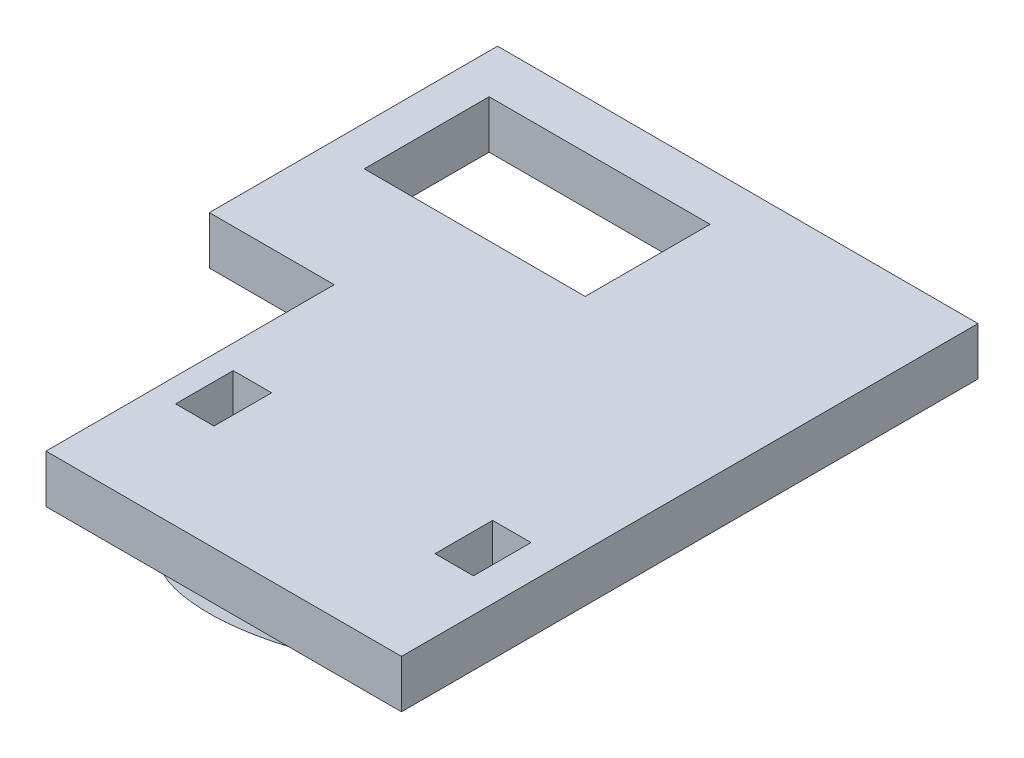
SolidWorks part; units mm, degrees
ref_plane "前视基准面" through (0, 0, 0) normal (0, 0, 1) x (1, 0, 0)
ref_plane "上视基准面" through (0, 0, 0) normal (0, 1, 0) x (1, 0, 0)
ref_plane "右视基准面" through (0, 0, 0) normal (1, 0, 0) x (0, 0, -1)
other "Configuration Table"
sketch "草图1" plane through (0, 0, 0) normal (0, 1, 0) x (1, 0, 0)
  line L0 (-12, 0) -> (-25, 0)
  line L1 (0, -30) -> (25, -30)
  line L2 (-25, 0) -> (-25, 30)
  line L3 (-25, 30) -> (25, 30)
  line L4 (25, -30) -> (25, 30)
  line L5 (-12, 0) -> (-12, -30)
  line L6 (-12, -30) -> (0, -30)
  point P0 (0, 0)
  dimension "D1" = 50
extrude "凸台-拉伸1" add sketch "草图1" along normal blind 5
sketch "草图3" plane through (0, 5, 0) normal (0, 1, 0) x (1, 0, 0)
  line L0 (25, 30) -> (-25, 30) construction
  line L1 (-20.8838, 25) -> (2.1162, 25)
  line L2 (-20.8838, 25) -> (-20.8838, 12)
  line L3 (-20.8838, 12) -> (2.1162, 12)
  line L4 (2.1162, 25) -> (2.1162, 12)
  line L5 (-20.8838, 25) -> (2.1162, 12) construction
  line L6 (-20.8838, 12) -> (2.1162, 25) construction
  point P0 (-9.3838, 18.5)
  dimension "D1" = 13
  dimension "D2" = 23
  dimension "D3" = 5
extrude "切除-拉伸1" cut sketch "草图3" against normal through all
sketch "草图4" plane through (0, 5, 0) normal (0, 1, 0) x (1, 0, 0)
  line L0 (17.4849, -13) -> (21.4849, -13)
  line L1 (-9.5151, -13) -> (-5.5151, -13)
  line L2 (-9.5151, -13) -> (-9.5151, -19)
  line L3 (-9.5151, -19) -> (-5.5151, -19)
  line L4 (-5.5151, -13) -> (-5.5151, -19)
  line L5 (-9.5151, -13) -> (-5.5151, -19) construction
  line L6 (-9.5151, -19) -> (-5.5151, -13) construction
  line L7 (17.4849, -13) -> (17.4849, -19)
  line L8 (17.4849, -19) -> (21.4849, -19)
  line L9 (21.4849, -13) -> (21.4849, -19)
  line L10 (-20.8838, 12) -> (2.1162, 12) construction
  line L11 (-12, -30) -> (25, -30) construction
  point P0 (-7.5151, -16)
  dimension "D1" = 23
  dimension "D2" = 25
  dimension "D3" = 6
  dimension "D4" = 4
  dimension "D5" = 11
extrude "切除-拉伸3" cut sketch "草图4" against normal up to next
ref_plane "基准面2" through (0, -5, 0) normal (0, -1, 0) x (-1, 0, 0)
sketch "草图7" plane through (0, -5, 0) normal (0, -1, 0) x (-1, 0, 0)
  line L0 (12, -13.3987) -> (-12, -13.3987) construction
ref_plane "基准面3" through (0, -8.7214, 3.1743) normal (0, -0.9397, 0.342) x (1, 0, 0)
sketch "草图2" plane through (0, 0, 0) normal (0, -1, 0) x (1, 0, 0)
  line L0 (0, 0) -> (0, 30.92) construction
  circle A0 centre (0, 9.6843) radius 12
  point P2 (0, 10.0126)
  point P5 (0, 11.5884)
  point P6 (0, 9.6843)
ref_plane "基准面4" through (0, 0, 0) normal (1, 0, 0) x (0, 0, 1)
sketch "草图8" plane through (0, -8.7214, 3.1743) normal (0, -0.9397, 0.342) x (1, 0, 0)
  circle A0 centre (0, 9.4743) radius 12
loft "放样3" add profiles "草图2", "草图8" connector at (0, 0, -2.3157) connector at (-0.5276, -9.5812, 0.8118)
sketch "草图10" plane through (0, -8.7214, 3.1743) normal (0, -0.9397, 0.342) x (1, 0, 0)
  circle A1 centre (0, 9.4743) radius 12
  circle A2 centre (0, 9.4743) radius 12
  dimension "D1" = 0
extrude "凸台-拉伸2" add sketch "草图10" along normal blind 5
